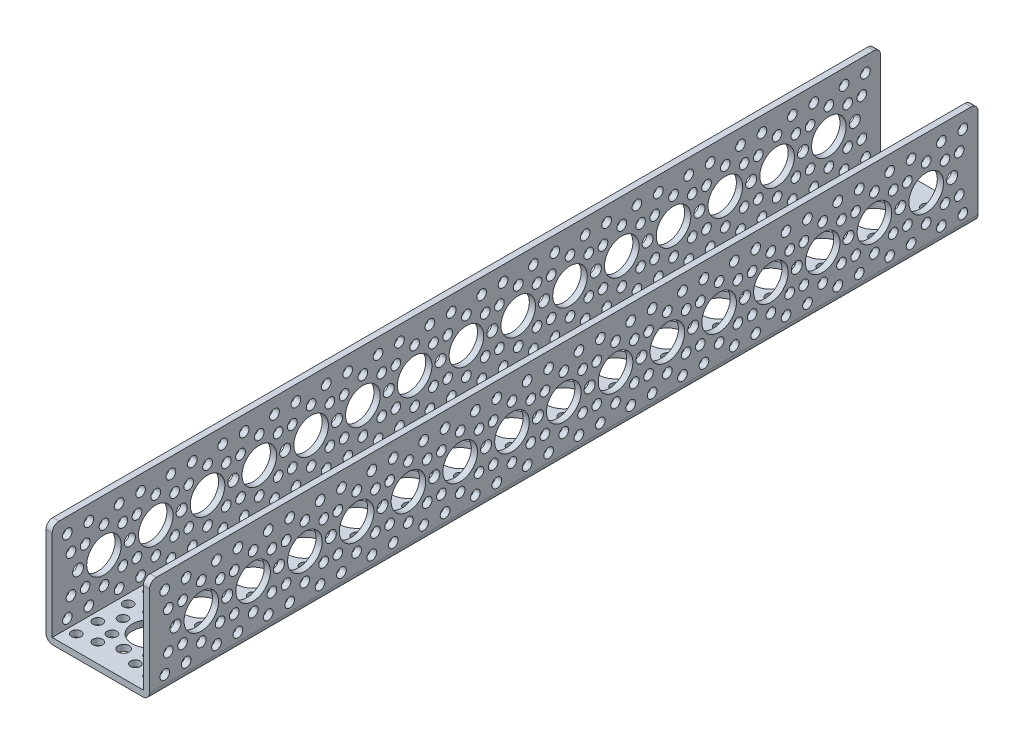
SolidWorks part; units mm, degrees
ref_plane "Front Plane" through (0, 0, 0) normal (0, 0, 1) x (1, 0, 0)
ref_plane "Top Plane" through (0, 0, 0) normal (0, 1, 0) x (1, 0, 0)
ref_plane "Right Plane" through (0, 0, 0) normal (1, 0, 0) x (0, 0, -1)
ref_plane "Plane1" through (0, 0, 0) normal (0, -1, 0) x (1, 0, 0)
sketch "Sketch1" plane through (0, 0, 0) normal (0, -1, 0) x (1, 0, 0)
  line L0 (38.1, 304.8) -> (0, 304.8)
  line L1 (0, 304.8) -> (0, 0)
  line L2 (0, 0) -> (38.1, 0)
  line L3 (38.1, 0) -> (38.1, 304.8)
extrude "Boss-Extrude1" add sketch "Sketch1" against normal blind 38.1
sketch "Sketch2" plane through (0, 0, 304.8) normal (0, 0, 1) x (1, 0, 0)
  line L0 (35.814, 38.1) -> (2.286, 38.1)
  line L1 (2.286, 38.1) -> (2.286, 2.286)
  line L2 (2.286, 2.286) -> (35.814, 2.286)
  line L3 (35.814, 2.286) -> (35.814, 38.1)
extrude "Cut-Extrude1" cut sketch "Sketch2" against normal through all
hole_wizard "Hole1" positions "Sketch4" profile "Sketch3" legacy
sketch "Sketch4" plane through (38.1, 0, 0) normal (1, 0, 0) x (0, 0, -1)
  point P0 (-38.1, 19.05)
  point P1 (-19.05, 19.05)
  point P2 (-57.15, 19.05)
  point P3 (-76.2, 19.05)
  point P4 (-95.25, 19.05)
  point P5 (-114.3, 19.05)
  point P6 (-133.35, 19.05)
  point P7 (-152.4, 19.05)
  point P8 (-171.45, 19.05)
  point P9 (-190.5, 19.05)
  point P10 (-209.55, 19.05)
  point P11 (-228.6, 19.05)
  point P12 (-247.65, 19.05)
  point P13 (-266.7, 19.05)
  point P14 (-285.75, 19.05)
sketch "Sketch3" plane through (38.1, 19.05, 38.1) normal (0, 1, 0) x (0, 0, -1)
  line L0 (0, 0) -> (0, 2.286)
  line L1 (0, 2.286) -> (6.3627, 2.286)
  line L2 (6.3627, 2.286) -> (6.3627, 0)
  line L3 (6.3627, 0) -> (0, 0)
  line L4 (0, 110) -> (0, -10) construction
  dimension "Diameter" = 12.7254
  dimension "Depth" = 2.286
hole_wizard "M3 Clearance Hole1" positions "Sketch6" profile "Sketch5" hole size "M3" standard "ANSI Metric"
sketch "Sketch6" plane through (38.1, 0, 0) normal (1, 0, 0) x (0, 0, -1)
  point P0 (-291.3296, 5.5796)
  point P1 (-297.8852, 12.1352)
  point P2 (-291.3296, 32.5204)
  point P3 (-297.8852, 25.9648)
  point P4 (-13.4704, 5.5796)
  point P5 (-6.9148, 12.1352)
  point P6 (-13.4704, 32.5204)
  point P7 (-6.9148, 25.9648)
  point P8 (-272.2796, 5.5796)
  point P9 (-253.2296, 5.5796)
  point P10 (-234.1796, 5.5796)
  point P11 (-215.1296, 5.5796)
  point P12 (-196.0796, 5.5796)
  point P13 (-177.0296, 5.5796)
  point P14 (-157.9796, 5.5796)
  point P15 (-138.9296, 5.5796)
  point P16 (-119.8796, 5.5796)
  point P17 (-100.8296, 5.5796)
  point P18 (-81.7796, 5.5796)
  point P19 (-62.7296, 5.5796)
  point P20 (-43.6796, 5.5796)
  point P21 (-24.6296, 5.5796)
  point P22 (-272.2796, 32.5204)
  point P23 (-253.2296, 32.5204)
  point P24 (-234.1796, 32.5204)
  point P25 (-215.1296, 32.5204)
  point P26 (-196.0796, 32.5204)
  point P27 (-177.0296, 32.5204)
  point P28 (-157.9796, 32.5204)
  point P29 (-138.9296, 32.5204)
  point P30 (-119.8796, 32.5204)
  point P31 (-100.8296, 32.5204)
  point P32 (-81.7796, 32.5204)
  point P33 (-62.7296, 32.5204)
  point P34 (-43.6796, 32.5204)
  point P35 (-24.6296, 32.5204)
  point P36 (-299.2204, 5.5796)
  point P37 (-299.2204, 32.5204)
  point P38 (-280.1704, 5.5796)
  point P39 (-280.1704, 32.5204)
  point P40 (-261.1204, 5.5796)
  point P41 (-261.1204, 32.5204)
  point P42 (-242.0704, 5.5796)
  point P43 (-242.0704, 32.5204)
  point P44 (-223.0204, 5.5796)
  point P45 (-223.0204, 32.5204)
  point P46 (-203.9704, 5.5796)
  point P47 (-203.9704, 32.5204)
  point P48 (-184.9204, 5.5796)
  point P49 (-184.9204, 32.5204)
  point P50 (-165.8704, 5.5796)
  point P51 (-165.8704, 32.5204)
  point P52 (-146.8204, 5.5796)
  point P53 (-146.8204, 32.5204)
  point P54 (-127.7704, 5.5796)
  point P55 (-127.7704, 32.5204)
  point P56 (-108.7204, 5.5796)
  point P57 (-108.7204, 32.5204)
  point P58 (-89.6704, 5.5796)
  point P59 (-89.6704, 32.5204)
  point P60 (-70.6204, 5.5796)
  point P61 (-70.6204, 32.5204)
  point P62 (-51.5704, 5.5796)
  point P63 (-51.5704, 32.5204)
  point P64 (-38.1, 9.271)
  point P65 (-45.0148, 12.1352)
  point P66 (-45.0148, 25.9648)
  point P67 (-38.1, 28.829)
  point P68 (-31.1852, 25.9648)
  point P69 (-31.1852, 12.1352)
  point P70 (-32.5204, 5.5796)
  point P71 (-32.5204, 32.5204)
  point P72 (-5.5796, 5.5796)
  point P73 (-5.5796, 32.5204)
  point P74 (-12.1352, 12.1352)
  point P75 (-19.05, 9.271)
  point P76 (-25.9648, 12.1352)
  point P77 (-25.9648, 25.9648)
  point P78 (-19.05, 28.829)
  point P79 (-12.1352, 25.9648)
  point P80 (-50.2352, 12.1352)
  point P81 (-69.2852, 12.1352)
  point P82 (-88.3352, 12.1352)
  point P83 (-107.3852, 12.1352)
  point P84 (-126.4352, 12.1352)
  point P85 (-145.4852, 12.1352)
  point P86 (-164.5352, 12.1352)
  point P87 (-183.5852, 12.1352)
  point P88 (-202.6352, 12.1352)
  point P89 (-221.6852, 12.1352)
  point P90 (-240.7352, 12.1352)
  point P91 (-259.7852, 12.1352)
  point P92 (-278.8352, 12.1352)
  point P93 (-50.2352, 25.9648)
  point P94 (-69.2852, 25.9648)
  point P95 (-88.3352, 25.9648)
  point P96 (-107.3852, 25.9648)
  point P97 (-126.4352, 25.9648)
  point P98 (-145.4852, 25.9648)
  point P99 (-164.5352, 25.9648)
  point P100 (-183.5852, 25.9648)
  point P101 (-202.6352, 25.9648)
  point P102 (-221.6852, 25.9648)
  point P103 (-240.7352, 25.9648)
  point P104 (-259.7852, 25.9648)
  point P105 (-278.8352, 25.9648)
  point P106 (-57.15, 28.829)
  point P107 (-76.2, 28.829)
  point P108 (-95.25, 28.829)
  point P109 (-114.3, 28.829)
  point P110 (-133.35, 28.829)
  point P111 (-152.4, 28.829)
  point P112 (-171.45, 28.829)
  point P113 (-190.5, 28.829)
  point P114 (-209.55, 28.829)
  point P115 (-228.6, 28.829)
  point P116 (-247.65, 28.829)
  point P117 (-266.7, 28.829)
  point P118 (-285.75, 28.829)
  point P119 (-64.0648, 25.9648)
  point P120 (-83.1148, 25.9648)
  point P121 (-102.1648, 25.9648)
  point P122 (-121.2148, 25.9648)
  point P123 (-140.2648, 25.9648)
  point P124 (-159.3148, 25.9648)
  point P125 (-178.3648, 25.9648)
  point P126 (-197.4148, 25.9648)
  point P127 (-216.4648, 25.9648)
  point P128 (-235.5148, 25.9648)
  point P129 (-254.5648, 25.9648)
  point P130 (-273.6148, 25.9648)
  point P131 (-292.6648, 25.9648)
  point P132 (-64.0648, 12.1352)
  point P133 (-83.1148, 12.1352)
  point P134 (-102.1648, 12.1352)
  point P135 (-121.2148, 12.1352)
  point P136 (-140.2648, 12.1352)
  point P137 (-159.3148, 12.1352)
  point P138 (-178.3648, 12.1352)
  point P139 (-197.4148, 12.1352)
  point P140 (-216.4648, 12.1352)
  point P141 (-235.5148, 12.1352)
  point P142 (-254.5648, 12.1352)
  point P143 (-273.6148, 12.1352)
  point P144 (-292.6648, 12.1352)
  point P145 (-57.15, 9.271)
  point P146 (-76.2, 9.271)
  point P147 (-95.25, 9.271)
  point P148 (-114.3, 9.271)
  point P149 (-133.35, 9.271)
  point P150 (-152.4, 9.271)
  point P151 (-171.45, 9.271)
  point P152 (-190.5, 9.271)
  point P153 (-209.55, 9.271)
  point P154 (-228.6, 9.271)
  point P155 (-247.65, 9.271)
  point P156 (-266.7, 9.271)
  point P157 (-285.75, 9.271)
sketch "Sketch5" plane through (38.1, 5.5796, 291.3296) normal (0, 1, 0) x (0, 0, -1)
  line L0 (0, 0) -> (0, 2.286)
  line L1 (0, 2.286) -> (1.778, 2.286)
  line L2 (1.778, 2.286) -> (1.778, 0)
  line L5 (1.778, 0) -> (0, 0)
  line L11 (0, -6.35) -> (0, 107.95) construction
  dimension "Thru Hole Dia." = 3.556
  dimension "Thru Hole Depth" = 2.286
hole_wizard "M3.5 Clearance Hole1" positions "Sketch8" profile "Sketch7" hole size "M3.5" standard "ANSI Metric"
sketch "Sketch8" plane through (38.1, 0, 0) normal (1, 0, 0) x (0, 0, -1)
  point P0 (-295.275, 19.05)
  point P1 (-276.225, 19.05)
  point P2 (-257.175, 19.05)
  point P3 (-238.125, 19.05)
  point P4 (-219.075, 19.05)
  point P5 (-200.025, 19.05)
  point P6 (-180.975, 19.05)
  point P7 (-161.925, 19.05)
  point P8 (-142.875, 19.05)
  point P9 (-123.825, 19.05)
  point P10 (-104.775, 19.05)
  point P11 (-85.725, 19.05)
  point P12 (-66.675, 19.05)
  point P13 (-47.625, 19.05)
  point P14 (-28.575, 19.05)
  point P15 (-9.525, 19.05)
sketch "Sketch7" plane through (38.1, 19.05, 295.275) normal (0, 1, 0) x (0, 0, -1)
  line L0 (0, 0) -> (0, 2.286)
  line L1 (0, 2.286) -> (2.032, 2.286)
  line L2 (2.032, 2.286) -> (2.032, 0)
  line L5 (2.032, 0) -> (0, 0)
  line L11 (0, -6.35) -> (0, 107.95) construction
  dimension "Thru Hole Dia." = 4.064
  dimension "Thru Hole Depth" = 2.286
hole_wizard "Hole2" positions "Sketch10" profile "Sketch9" legacy
sketch "Sketch10" plane through (0, 0, 0) normal (0, -1, 0) x (-1, 0, 0)
  point P0 (-19.05, -285.75)
  point P1 (-19.05, -266.7)
  point P2 (-19.05, -247.65)
  point P3 (-19.05, -228.6)
  point P4 (-19.05, -209.55)
  point P5 (-19.05, -190.5)
  point P6 (-19.05, -171.45)
  point P7 (-19.05, -152.4)
  point P8 (-19.05, -133.35)
  point P9 (-19.05, -114.3)
  point P10 (-19.05, -95.25)
  point P11 (-19.05, -76.2)
  point P12 (-19.05, -57.15)
  point P13 (-19.05, -38.1)
  point P14 (-19.05, -19.05)
sketch "Sketch9" plane through (19.05, 0, 285.75) normal (1, 0, 0) x (0, 0, -1)
  line L0 (0, 0) -> (0, 38.1)
  line L1 (0, 38.1) -> (6.3627, 38.1)
  line L2 (6.3627, 38.1) -> (6.3627, 0)
  line L3 (6.3627, 0) -> (0, 0)
  line L4 (0, 110) -> (0, -10) construction
  dimension "Diameter" = 12.7254
  dimension "Depth" = 38.1
hole_wizard "M3.5 Clearance Hole2" positions "Sketch12" profile "Sketch11" hole size "M3.5" standard "ANSI Metric"
sketch "Sketch12" plane through (0, 0, 0) normal (0, -1, 0) x (-1, 0, 0)
  point P0 (-19.05, -295.275)
  point P1 (-19.05, -276.225)
  point P2 (-19.05, -257.175)
  point P3 (-19.05, -238.125)
  point P4 (-19.05, -219.075)
  point P5 (-19.05, -200.025)
  point P6 (-19.05, -180.975)
  point P7 (-19.05, -161.925)
  point P8 (-19.05, -142.875)
  point P9 (-19.05, -123.825)
  point P10 (-19.05, -104.775)
  point P11 (-19.05, -85.725)
  point P12 (-19.05, -66.675)
  point P13 (-19.05, -47.625)
  point P14 (-19.05, -28.575)
  point P15 (-19.05, -9.525)
sketch "Sketch11" plane through (19.05, 0, 295.275) normal (1, 0, 0) x (0, 0, -1)
  line L0 (0, 0) -> (0, 38.1)
  line L1 (0, 38.1) -> (2.032, 38.1)
  line L2 (2.032, 38.1) -> (2.032, 0)
  line L5 (2.032, 0) -> (0, 0)
  line L11 (0, -6.35) -> (0, 107.95) construction
  dimension "Thru Hole Dia." = 4.064
  dimension "Thru Hole Depth" = 38.1
hole_wizard "M3 Clearance Hole2" positions "Sketch14" profile "Sketch13" hole size "M3" standard "ANSI Metric"
sketch "Sketch14" plane through (0, 0, 0) normal (0, -1, 0) x (-1, 0, 0)
  point P0 (-5.5796, -299.2204)
  point P1 (-5.5796, -291.3296)
  point P2 (-12.1352, -297.8852)
  point P3 (-32.5204, -299.2204)
  point P4 (-32.5204, -291.3296)
  point P5 (-25.9648, -297.8852)
  point P6 (-5.5796, -280.1704)
  point P7 (-5.5796, -272.2796)
  point P8 (-32.5204, -280.1704)
  point P9 (-32.5204, -272.2796)
  point P10 (-5.5796, -261.1204)
  point P11 (-5.5796, -253.2296)
  point P12 (-32.5204, -261.1204)
  point P13 (-32.5204, -253.2296)
  point P14 (-5.5796, -242.0704)
  point P15 (-5.5796, -234.1796)
  point P16 (-32.5204, -242.0704)
  point P17 (-32.5204, -234.1796)
  point P18 (-5.5796, -223.0204)
  point P19 (-5.5796, -215.1296)
  point P20 (-32.5204, -223.0204)
  point P21 (-32.5204, -215.1296)
  point P22 (-5.5796, -203.9704)
  point P23 (-5.5796, -196.0796)
  point P24 (-32.5204, -203.9704)
  point P25 (-32.5204, -196.0796)
  point P26 (-5.5796, -184.9204)
  point P27 (-5.5796, -177.0296)
  point P28 (-32.5204, -184.9204)
  point P29 (-32.5204, -177.0296)
  point P30 (-5.5796, -165.8704)
  point P31 (-5.5796, -157.9796)
  point P32 (-32.5204, -165.8704)
  point P33 (-32.5204, -157.9796)
  point P34 (-5.5796, -146.8204)
  point P35 (-5.5796, -138.9296)
  point P36 (-32.5204, -146.8204)
  point P37 (-32.5204, -138.9296)
  point P38 (-5.5796, -127.7704)
  point P39 (-5.5796, -119.8796)
  point P40 (-32.5204, -127.7704)
  point P41 (-32.5204, -119.8796)
  point P42 (-5.5796, -108.7204)
  point P43 (-5.5796, -100.8296)
  point P44 (-32.5204, -108.7204)
  point P45 (-32.5204, -100.8296)
  point P46 (-5.5796, -89.6704)
  point P47 (-5.5796, -81.7796)
  point P48 (-32.5204, -89.6704)
  point P49 (-32.5204, -81.7796)
  point P50 (-5.5796, -70.6204)
  point P51 (-5.5796, -62.7296)
  point P52 (-32.5204, -70.6204)
  point P53 (-32.5204, -62.7296)
  point P54 (-5.5796, -51.5704)
  point P55 (-5.5796, -43.6796)
  point P56 (-32.5204, -51.5704)
  point P57 (-32.5204, -43.6796)
  point P58 (-12.1352, -278.8352)
  point P59 (-9.271, -285.75)
  point P60 (-12.1352, -292.6648)
  point P61 (-25.9648, -292.6648)
  point P62 (-28.829, -285.75)
  point P63 (-25.9648, -278.8352)
  point P64 (-12.1352, -259.7852)
  point P65 (-9.271, -266.7)
  point P66 (-12.1352, -273.6148)
  point P67 (-25.9648, -273.6148)
  point P68 (-28.829, -266.7)
  point P69 (-25.9648, -259.7852)
  point P70 (-12.1352, -240.7352)
  point P71 (-9.271, -247.65)
  point P72 (-12.1352, -254.5648)
  point P73 (-25.9648, -254.5648)
  point P74 (-28.829, -247.65)
  point P75 (-25.9648, -240.7352)
  point P76 (-12.1352, -221.6852)
  point P77 (-9.271, -228.6)
  point P78 (-12.1352, -235.5148)
  point P79 (-25.9648, -235.5148)
  point P80 (-28.829, -228.6)
  point P81 (-25.9648, -221.6852)
  point P82 (-12.1352, -202.6352)
  point P83 (-9.271, -209.55)
  point P84 (-12.1352, -216.4648)
  point P85 (-25.9648, -216.4648)
  point P86 (-28.829, -209.55)
  point P87 (-25.9648, -202.6352)
  point P88 (-12.1352, -183.5852)
  point P89 (-9.271, -190.5)
  point P90 (-12.1352, -197.4148)
  point P91 (-25.9648, -197.4148)
  point P92 (-28.829, -190.5)
  point P93 (-25.9648, -183.5852)
  point P94 (-12.1352, -164.5352)
  point P95 (-9.271, -171.45)
  point P96 (-12.1352, -178.3648)
  point P97 (-25.9648, -178.3648)
  point P98 (-28.829, -171.45)
  point P99 (-25.9648, -164.5352)
  point P100 (-12.1352, -145.4852)
  point P101 (-9.271, -152.4)
  point P102 (-12.1352, -159.3148)
  point P103 (-25.9648, -159.3148)
  point P104 (-28.829, -152.4)
  point P105 (-25.9648, -145.4852)
  point P106 (-12.1352, -126.4352)
  point P107 (-9.271, -133.35)
  point P108 (-12.1352, -140.2648)
  point P109 (-25.9648, -140.2648)
  point P110 (-28.829, -133.35)
  point P111 (-25.9648, -126.4352)
  point P112 (-12.1352, -107.3852)
  point P113 (-9.271, -114.3)
  point P114 (-12.1352, -121.2148)
  point P115 (-25.9648, -121.2148)
  point P116 (-28.829, -114.3)
  point P117 (-25.9648, -107.3852)
  point P118 (-12.1352, -88.3352)
  point P119 (-9.271, -95.25)
  point P120 (-12.1352, -102.1648)
  point P121 (-25.9648, -102.1648)
  point P122 (-28.829, -95.25)
  point P123 (-25.9648, -88.3352)
  point P124 (-12.1352, -69.2852)
  point P125 (-9.271, -76.2)
  point P126 (-12.1352, -83.1148)
  point P127 (-25.9648, -83.1148)
  point P128 (-28.829, -76.2)
  point P129 (-25.9648, -69.2852)
  point P130 (-12.1352, -50.2352)
  point P131 (-9.271, -57.15)
  point P132 (-12.1352, -64.0648)
  point P133 (-25.9648, -64.0648)
  point P134 (-28.829, -57.15)
  point P135 (-25.9648, -50.2352)
  point P136 (-9.271, -38.1)
  point P137 (-12.1352, -45.0148)
  point P138 (-25.9648, -45.0148)
  point P139 (-28.829, -38.1)
  point P140 (-5.5796, -32.5204)
  point P141 (-5.5796, -24.6296)
  point P142 (-12.1352, -31.1852)
  point P143 (-32.5204, -32.5204)
  point P144 (-32.5204, -24.6296)
  point P145 (-25.9648, -31.1852)
  point P146 (-5.5796, -5.5796)
  point P147 (-5.5796, -13.4704)
  point P148 (-12.1352, -6.9148)
  point P149 (-32.5204, -5.5796)
  point P150 (-32.5204, -13.4704)
  point P151 (-25.9648, -6.9148)
  point P152 (-12.1352, -12.1352)
  point P153 (-9.271, -19.05)
  point P154 (-12.1352, -25.9648)
  point P155 (-25.9648, -25.9648)
  point P156 (-28.829, -19.05)
  point P157 (-25.9648, -12.1352)
sketch "Sketch13" plane through (5.5796, 0, 299.2204) normal (1, 0, 0) x (0, 0, -1)
  line L0 (0, 0) -> (0, 38.1)
  line L1 (0, 38.1) -> (1.778, 38.1)
  line L2 (1.778, 38.1) -> (1.778, 0)
  line L5 (1.778, 0) -> (0, 0)
  line L11 (0, -6.35) -> (0, 107.95) construction
  dimension "Thru Hole Dia." = 3.556
  dimension "Thru Hole Depth" = 38.1
hole_wizard "Hole3" positions "Sketch16" profile "Sketch15" legacy
sketch "Sketch16" plane through (0, 0, 0) normal (-1, 0, 0) x (0, 0, 1)
  point P0 (38.1, 19.05)
  point P1 (19.05, 19.05)
  point P2 (57.15, 19.05)
  point P3 (76.2, 19.05)
  point P4 (95.25, 19.05)
  point P5 (114.3, 19.05)
  point P6 (133.35, 19.05)
  point P7 (152.4, 19.05)
  point P8 (171.45, 19.05)
  point P9 (190.5, 19.05)
  point P10 (209.55, 19.05)
  point P11 (228.6, 19.05)
  point P12 (247.65, 19.05)
  point P13 (266.7, 19.05)
  point P14 (285.75, 19.05)
sketch "Sketch15" plane through (0, 19.05, 38.1) normal (0, 1, 0) x (0, 0, 1)
  line L0 (0, 0) -> (0, 38.1)
  line L1 (0, 38.1) -> (6.3627, 38.1)
  line L2 (6.3627, 38.1) -> (6.3627, 0)
  line L3 (6.3627, 0) -> (0, 0)
  line L4 (0, 110) -> (0, -10) construction
  dimension "Diameter" = 12.7254
  dimension "Depth" = 38.1
hole_wizard "M3 Clearance Hole3" positions "Sketch18" profile "Sketch17" hole size "M3" standard "ANSI Metric"
sketch "Sketch18" plane through (0, 0, 0) normal (-1, 0, 0) x (0, 0, 1)
  point P0 (291.3296, 5.5796)
  point P1 (297.8852, 12.1352)
  point P2 (291.3296, 32.5204)
  point P3 (297.8852, 25.9648)
  point P4 (13.4704, 5.5796)
  point P5 (6.9148, 12.1352)
  point P6 (13.4704, 32.5204)
  point P7 (6.9148, 25.9648)
  point P8 (272.2796, 5.5796)
  point P9 (253.2296, 5.5796)
  point P10 (234.1796, 5.5796)
  point P11 (215.1296, 5.5796)
  point P12 (196.0796, 5.5796)
  point P13 (177.0296, 5.5796)
  point P14 (157.9796, 5.5796)
  point P15 (138.9296, 5.5796)
  point P16 (119.8796, 5.5796)
  point P17 (100.8296, 5.5796)
  point P18 (81.7796, 5.5796)
  point P19 (62.7296, 5.5796)
  point P20 (43.6796, 5.5796)
  point P21 (24.6296, 5.5796)
  point P22 (272.2796, 32.5204)
  point P23 (253.2296, 32.5204)
  point P24 (234.1796, 32.5204)
  point P25 (215.1296, 32.5204)
  point P26 (196.0796, 32.5204)
  point P27 (177.0296, 32.5204)
  point P28 (157.9796, 32.5204)
  point P29 (138.9296, 32.5204)
  point P30 (119.8796, 32.5204)
  point P31 (100.8296, 32.5204)
  point P32 (81.7796, 32.5204)
  point P33 (62.7296, 32.5204)
  point P34 (43.6796, 32.5204)
  point P35 (24.6296, 32.5204)
  point P36 (299.2204, 5.5796)
  point P37 (299.2204, 32.5204)
  point P38 (280.1704, 5.5796)
  point P39 (280.1704, 32.5204)
  point P40 (261.1204, 5.5796)
  point P41 (261.1204, 32.5204)
  point P42 (242.0704, 5.5796)
  point P43 (242.0704, 32.5204)
  point P44 (223.0204, 5.5796)
  point P45 (223.0204, 32.5204)
  point P46 (203.9704, 5.5796)
  point P47 (203.9704, 32.5204)
  point P48 (184.9204, 5.5796)
  point P49 (184.9204, 32.5204)
  point P50 (165.8704, 5.5796)
  point P51 (165.8704, 32.5204)
  point P52 (146.8204, 5.5796)
  point P53 (146.8204, 32.5204)
  point P54 (127.7704, 5.5796)
  point P55 (127.7704, 32.5204)
  point P56 (108.7204, 5.5796)
  point P57 (108.7204, 32.5204)
  point P58 (89.6704, 5.5796)
  point P59 (89.6704, 32.5204)
  point P60 (70.6204, 5.5796)
  point P61 (70.6204, 32.5204)
  point P62 (51.5704, 5.5796)
  point P63 (51.5704, 32.5204)
  point P64 (31.1852, 12.1352)
  point P65 (38.1, 9.271)
  point P66 (45.0148, 12.1352)
  point P67 (45.0148, 25.9648)
  point P68 (38.1, 28.829)
  point P69 (31.1852, 25.9648)
  point P70 (32.5204, 5.5796)
  point P71 (32.5204, 32.5204)
  point P72 (5.5796, 5.5796)
  point P73 (5.5796, 32.5204)
  point P74 (12.1352, 12.1352)
  point P75 (19.05, 9.271)
  point P76 (25.9648, 12.1352)
  point P77 (25.9648, 25.9648)
  point P78 (19.05, 28.829)
  point P79 (12.1352, 25.9648)
  point P80 (50.2352, 25.9648)
  point P81 (69.2852, 25.9648)
  point P82 (88.3352, 25.9648)
  point P83 (107.3852, 25.9648)
  point P84 (126.4352, 25.9648)
  point P85 (145.4852, 25.9648)
  point P86 (164.5352, 25.9648)
  point P87 (183.5852, 25.9648)
  point P88 (202.6352, 25.9648)
  point P89 (221.6852, 25.9648)
  point P90 (240.7352, 25.9648)
  point P91 (259.7852, 25.9648)
  point P92 (278.8352, 25.9648)
  point P93 (57.15, 28.829)
  point P94 (76.2, 28.829)
  point P95 (95.25, 28.829)
  point P96 (114.3, 28.829)
  point P97 (133.35, 28.829)
  point P98 (152.4, 28.829)
  point P99 (171.45, 28.829)
  point P100 (190.5, 28.829)
  point P101 (209.55, 28.829)
  point P102 (228.6, 28.829)
  point P103 (247.65, 28.829)
  point P104 (266.7, 28.829)
  point P105 (285.75, 28.829)
  point P106 (64.0648, 25.9648)
  point P107 (83.1148, 25.9648)
  point P108 (102.1648, 25.9648)
  point P109 (121.2148, 25.9648)
  point P110 (140.2648, 25.9648)
  point P111 (159.3148, 25.9648)
  point P112 (178.3648, 25.9648)
  point P113 (197.4148, 25.9648)
  point P114 (216.4648, 25.9648)
  point P115 (235.5148, 25.9648)
  point P116 (254.5648, 25.9648)
  point P117 (273.6148, 25.9648)
  point P118 (292.6648, 25.9648)
  point P119 (64.0648, 12.1352)
  point P120 (83.1148, 12.1352)
  point P121 (102.1648, 12.1352)
  point P122 (121.2148, 12.1352)
  point P123 (140.2648, 12.1352)
  point P124 (159.3148, 12.1352)
  point P125 (178.3648, 12.1352)
  point P126 (197.4148, 12.1352)
  point P127 (216.4648, 12.1352)
  point P128 (235.5148, 12.1352)
  point P129 (254.5648, 12.1352)
  point P130 (273.6148, 12.1352)
  point P131 (292.6648, 12.1352)
  point P132 (57.15, 9.271)
  point P133 (76.2, 9.271)
  point P134 (95.25, 9.271)
  point P135 (114.3, 9.271)
  point P136 (133.35, 9.271)
  point P137 (152.4, 9.271)
  point P138 (171.45, 9.271)
  point P139 (190.5, 9.271)
  point P140 (209.55, 9.271)
  point P141 (228.6, 9.271)
  point P142 (247.65, 9.271)
  point P143 (266.7, 9.271)
  point P144 (285.75, 9.271)
  point P145 (50.2352, 12.1352)
  point P146 (69.2852, 12.1352)
  point P147 (88.3352, 12.1352)
  point P148 (107.3852, 12.1352)
  point P149 (126.4352, 12.1352)
  point P150 (145.4852, 12.1352)
  point P151 (164.5352, 12.1352)
  point P152 (183.5852, 12.1352)
  point P153 (202.6352, 12.1352)
  point P154 (221.6852, 12.1352)
  point P155 (240.7352, 12.1352)
  point P156 (259.7852, 12.1352)
  point P157 (278.8352, 12.1352)
sketch "Sketch17" plane through (0, 5.5796, 291.3296) normal (0, 1, 0) x (0, 0, 1)
  line L0 (0, 0) -> (0, 38.1)
  line L1 (0, 38.1) -> (1.778, 38.1)
  line L2 (1.778, 38.1) -> (1.778, 0)
  line L5 (1.778, 0) -> (0, 0)
  line L11 (0, -6.35) -> (0, 107.95) construction
  dimension "Thru Hole Dia." = 3.556
  dimension "Thru Hole Depth" = 38.1
hole_wizard "M3.5 Clearance Hole3" positions "Sketch20" profile "Sketch19" hole size "M3.5" standard "ANSI Metric"
sketch "Sketch20" plane through (0, 0, 0) normal (-1, 0, 0) x (0, 0, 1)
  point P0 (295.275, 19.05)
  point P1 (276.225, 19.05)
  point P2 (257.175, 19.05)
  point P3 (238.125, 19.05)
  point P4 (219.075, 19.05)
  point P5 (200.025, 19.05)
  point P6 (180.975, 19.05)
  point P7 (161.925, 19.05)
  point P8 (142.875, 19.05)
  point P9 (123.825, 19.05)
  point P10 (104.775, 19.05)
  point P11 (85.725, 19.05)
  point P12 (66.675, 19.05)
  point P13 (47.625, 19.05)
  point P14 (28.575, 19.05)
  point P15 (9.525, 19.05)
sketch "Sketch19" plane through (0, 19.05, 295.275) normal (0, 1, 0) x (0, 0, 1)
  line L0 (0, 0) -> (0, 38.1)
  line L1 (0, 38.1) -> (2.032, 38.1)
  line L2 (2.032, 38.1) -> (2.032, 0)
  line L5 (2.032, 0) -> (0, 0)
  line L11 (0, -6.35) -> (0, 107.95) construction
  dimension "Thru Hole Dia." = 4.064
  dimension "Thru Hole Depth" = 38.1
fillet "Fillet1" radius 2.54 6 edges at (1.143, 38.1, 304.8) (36.957, 38.1, 304.8) (36.957, 38.1, 0) (38.1, 0, 152.4) (1.143, 38.1, 0) (0, 0, 152.4) tangent propagation no
